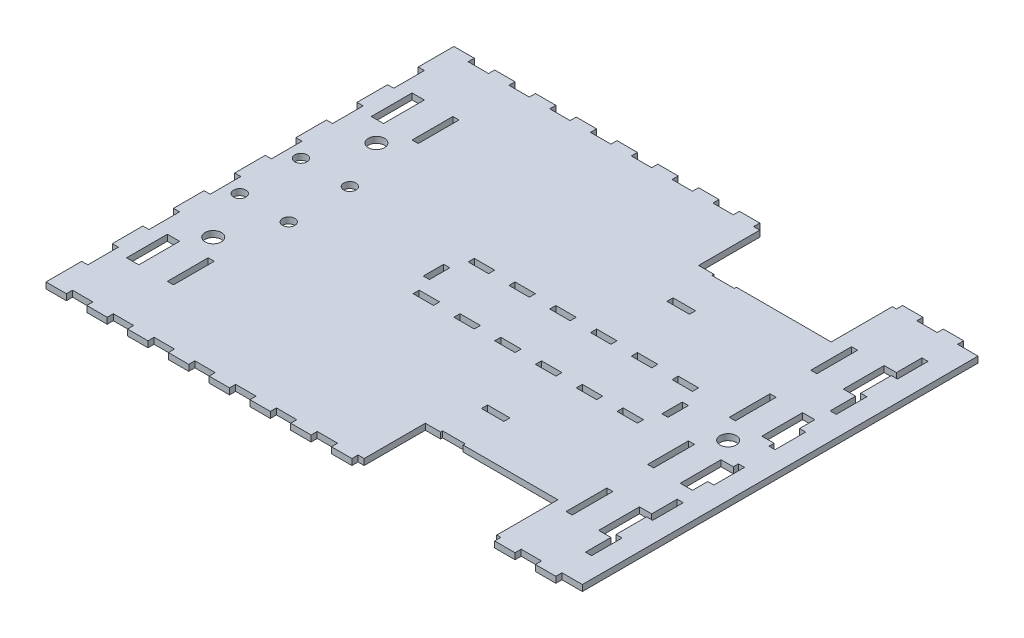
SolidWorks part; units mm, degrees
ref_plane "Front Plane" through (0, 0, 0) normal (0, 0, 1) x (1, 0, 0)
ref_plane "Top Plane" through (0, 0, 0) normal (0, 1, 0) x (1, 0, 0)
ref_plane "Right Plane" through (0, 0, 0) normal (1, 0, 0) x (0, 0, -1)
sketch "Sketch3" plane through (0, 0, 0) normal (0, 1, 0) x (1, 0, 0)
  line L0 (0, 0) -> (-300, 0) construction
  line L1 (-300, -97) -> (-300, 97)
  line L2 (-290, 100) -> (-300, 100)
  line L3 (-290, 97) -> (-290, 100)
  line L4 (-280, 97) -> (-290, 97)
  line L5 (-300, 100) -> (-300, 97)
  line L6 (-270, 100) -> (-280, 100)
  line L7 (-270, 97) -> (-270, 100)
  line L8 (-260, 97) -> (-270, 97)
  line L9 (-280, 100) -> (-280, 97)
  line L10 (-250, 100) -> (-260, 100)
  line L11 (-250, 97) -> (-250, 100)
  line L12 (-240, 97) -> (-250, 97)
  line L13 (-260, 100) -> (-260, 97)
  line L14 (-150, -100) -> (-150, 100) construction
  line L15 (-230, 100) -> (-240, 100)
  line L16 (-230, 97) -> (-230, 100)
  line L17 (-220, 97) -> (-230, 97)
  line L18 (-240, 100) -> (-240, 97)
  line L19 (-210, 100) -> (-220, 100)
  line L20 (-210, 97) -> (-210, 100)
  line L21 (-200, 97) -> (-210, 97)
  line L22 (-40, 97) -> (-40, -97)
  line L23 (-50, 37.5) -> (-53, 37.5)
  line L24 (-50, 7.5) -> (-53, 7.5)
  line L25 (-50, -45.947) -> (-50, 45.947) construction
  line L26 (-247, 37.5) -> (-250, 37.5) construction
  line L27 (-247, 7.5) -> (-250, 7.5) construction
  line L28 (-247, 48.5) -> (-247, -48.5) construction
  line L29 (-247, 48.5) -> (-223, 48.5) construction
  line L30 (-223, 48.5) -> (-223, -48.5) construction
  line L31 (-210, 15) -> (-90, 15) construction
  line L32 (-90, 15) -> (-90, 5) construction
  line L33 (-50, 7.5) -> (-50, 22.5)
  line L34 (-220, 100) -> (-220, 97)
  line L35 (-190, 100) -> (-200, 100)
  line L36 (-190, 97) -> (-190, 100)
  line L37 (-180, 97) -> (-190, 97)
  line L38 (-200, 100) -> (-200, 97)
  line L39 (-170, 100) -> (-180, 100)
  line L40 (-170, 97) -> (-170, 100)
  line L41 (-160, 97) -> (-170, 97)
  line L42 (-180, 100) -> (-180, 97)
  line L43 (-150, 100) -> (-160, 100)
  line L44 (-150, 97) -> (-150, 100)
  line L45 (-140, 97) -> (-150, 97)
  line L46 (-160, 100) -> (-160, 97)
  line L47 (-130, 100) -> (-140, 100)
  line L48 (-130, 97) -> (-130, 100)
  line L49 (-120, 97) -> (-130, 97)
  line L50 (-140, 100) -> (-140, 97)
  line L51 (-110, 100) -> (-120, 100)
  line L52 (-110, 97) -> (-110, 100)
  line L53 (-100, 97) -> (-110, 97)
  line L54 (-120, 100) -> (-120, 97)
  line L55 (-90, 100) -> (-100, 100)
  line L56 (-90, 97) -> (-90, 100)
  line L57 (-80, 97) -> (-90, 97)
  line L58 (-100, 100) -> (-100, 97)
  line L59 (-70, 100) -> (-80, 100)
  line L60 (-70, 97) -> (-70, 100)
  line L61 (-60, 97) -> (-70, 97)
  line L62 (-80, 100) -> (-80, 97)
  line L63 (-50, 100) -> (-60, 100)
  line L64 (-50, 97) -> (-50, 100)
  line L65 (-40, 97) -> (-50, 97)
  line L66 (-60, 100) -> (-60, 97)
  line L67 (-50, 22.5) -> (-53, 22.5)
  line L68 (-210, -15) -> (-90, -15) construction
  line L69 (-53, 7.5) -> (-53, 22.5)
  line L70 (-50, 37.5) -> (-50, 52.5)
  line L71 (-50, 52.5) -> (-53, 52.5)
  line L72 (-53, 37.5) -> (-53, 52.5)
  line L73 (-50, 67.5) -> (-53, 67.5)
  line L74 (-50, 67.5) -> (-50, 82.5)
  line L75 (-50, 82.5) -> (-53, 82.5)
  line L76 (-60, -100) -> (-60, -97)
  line L77 (-40, -97) -> (-50, -97)
  line L78 (-50, -97) -> (-50, -100)
  line L79 (-50, -100) -> (-60, -100)
  line L80 (-80, -100) -> (-80, -97)
  line L81 (-60, -97) -> (-70, -97)
  line L82 (-70, -97) -> (-70, -100)
  line L83 (-70, -100) -> (-80, -100)
  line L84 (-100, -100) -> (-100, -97)
  line L85 (-80, -97) -> (-90, -97)
  line L86 (-90, -97) -> (-90, -100)
  line L87 (-90, -100) -> (-100, -100)
  line L88 (-120, -100) -> (-120, -97)
  line L89 (-100, -97) -> (-110, -97)
  line L90 (-110, -97) -> (-110, -100)
  line L91 (-110, -100) -> (-120, -100)
  line L92 (-140, -100) -> (-140, -97)
  line L93 (-120, -97) -> (-130, -97)
  line L94 (-130, -97) -> (-130, -100)
  line L95 (-130, -100) -> (-140, -100)
  line L96 (-160, -100) -> (-160, -97)
  line L97 (-140, -97) -> (-150, -97)
  line L98 (-150, -97) -> (-150, -100)
  line L99 (-150, -100) -> (-160, -100)
  line L100 (-180, -100) -> (-180, -97)
  line L101 (-160, -97) -> (-170, -97)
  line L102 (-170, -97) -> (-170, -100)
  line L103 (-170, -100) -> (-180, -100)
  line L104 (-200, -100) -> (-200, -97)
  line L105 (-180, -97) -> (-190, -97)
  line L106 (-190, -97) -> (-190, -100)
  line L107 (-190, -100) -> (-200, -100)
  line L108 (-247, -48.5) -> (-223, -48.5) construction
  line L109 (-247, 7.5) -> (-247, 22.5) construction
  line L110 (-220, -100) -> (-220, -97)
  line L111 (-53, 67.5) -> (-53, 82.5)
  line L112 (-53, -67.5) -> (-53, -82.5)
  line L113 (-50, -82.5) -> (-53, -82.5)
  line L114 (-200, -97) -> (-210, -97)
  line L115 (-210, -97) -> (-210, -100)
  line L116 (-210, -100) -> (-220, -100)
  line L117 (-240, -100) -> (-240, -97)
  line L118 (-220, -97) -> (-230, -97)
  line L119 (-230, -97) -> (-230, -100)
  line L120 (-230, -100) -> (-240, -100)
  line L121 (-50, -67.5) -> (-50, -82.5)
  line L122 (-260, -100) -> (-260, -97)
  line L123 (-240, -97) -> (-250, -97)
  line L124 (-250, -97) -> (-250, -100)
  line L125 (-250, -100) -> (-260, -100)
  line L126 (-280, -100) -> (-280, -97)
  line L127 (-260, -97) -> (-270, -97)
  line L128 (-270, -97) -> (-270, -100)
  line L129 (-270, -100) -> (-280, -100)
  line L130 (-300, -100) -> (-300, -97)
  line L131 (-210, 15) -> (-210, -15) construction
  line L132 (-115, 15) -> (-125, 15)
  line L133 (-90, 5) -> (-93, 5)
  line L134 (-90, 5) -> (-90, -5)
  line L135 (-90, -5) -> (-93, -5)
  line L136 (-93, 5) -> (-93, -5)
  line L137 (-95, 15) -> (-105, 15)
  line L138 (-95, 15) -> (-95, 12)
  line L139 (-95, 12) -> (-105, 12)
  line L140 (-105, 15) -> (-105, 12)
  line L141 (-115, 12) -> (-125, 12)
  line L142 (-125, 15) -> (-125, 12)
  line L143 (-135, 15) -> (-145, 15)
  line L144 (-135, 12) -> (-145, 12)
  line L145 (-145, 15) -> (-145, 12)
  line L146 (-155, 15) -> (-165, 15)
  line L147 (-155, 12) -> (-165, 12)
  line L148 (-165, 15) -> (-165, 12)
  line L149 (-175, 15) -> (-185, 15)
  line L150 (-175, 12) -> (-185, 12)
  line L151 (-185, 15) -> (-185, 12)
  line L152 (-195, 15) -> (-205, 15)
  line L153 (-195, 12) -> (-205, 12)
  line L154 (-205, 15) -> (-205, 12)
  line L155 (-195, 12) -> (-195, 15)
  line L156 (-175, 12) -> (-175, 15)
  line L157 (-155, 12) -> (-155, 15)
  line L158 (-135, 12) -> (-135, 15)
  line L159 (-115, 12) -> (-115, 15)
  line L160 (-207, 5) -> (-207, -5)
  line L161 (-210, -5) -> (-207, -5)
  line L162 (-210, 5) -> (-210, -5)
  line L163 (-210, 5) -> (-207, 5)
  line L164 (-115, -12) -> (-115, -15)
  line L165 (-135, -12) -> (-135, -15)
  line L166 (-155, -12) -> (-155, -15)
  line L167 (-175, -12) -> (-175, -15)
  line L168 (-195, -12) -> (-195, -15)
  line L169 (-205, -15) -> (-205, -12)
  line L170 (-195, -12) -> (-205, -12)
  line L171 (-195, -15) -> (-205, -15)
  line L172 (-185, -15) -> (-185, -12)
  line L173 (-175, -12) -> (-185, -12)
  line L174 (-175, -15) -> (-185, -15)
  line L175 (-165, -15) -> (-165, -12)
  line L176 (-155, -12) -> (-165, -12)
  line L177 (-155, -15) -> (-165, -15)
  line L178 (-145, -15) -> (-145, -12)
  line L179 (-135, -12) -> (-145, -12)
  line L180 (-135, -15) -> (-145, -15)
  line L181 (-125, -15) -> (-125, -12)
  line L182 (-115, -12) -> (-125, -12)
  line L183 (-105, -15) -> (-105, -12)
  line L184 (-95, -12) -> (-105, -12)
  line L185 (-95, -15) -> (-95, -12)
  line L186 (-95, -15) -> (-105, -15)
  line L187 (-115, -15) -> (-125, -15)
  line L188 (-247, 22.5) -> (-250, 22.5) construction
  line L189 (-250, 7.5) -> (-250, 22.5) construction
  line L190 (-247, 37.5) -> (-247, 52.5) construction
  line L191 (-247, 52.5) -> (-250, 52.5) construction
  line L192 (-250, 37.5) -> (-250, 52.5) construction
  line L193 (-247, 67.5) -> (-250, 67.5) construction
  line L194 (-247, 67.5) -> (-247, 82.5) construction
  line L195 (-247, 82.5) -> (-250, 82.5) construction
  line L196 (-250, 67.5) -> (-250, 82.5) construction
  line L197 (-250, -67.5) -> (-250, -82.5) construction
  line L198 (-247, -82.5) -> (-250, -82.5) construction
  line L199 (-247, -67.5) -> (-247, -82.5) construction
  line L200 (-247, -67.5) -> (-250, -67.5) construction
  line L201 (-250, -37.5) -> (-250, -52.5) construction
  line L202 (-247, -52.5) -> (-250, -52.5) construction
  line L203 (-247, -37.5) -> (-247, -52.5) construction
  line L204 (-250, -7.5) -> (-250, -22.5) construction
  line L205 (-247, -22.5) -> (-250, -22.5) construction
  line L206 (-247, -7.5) -> (-247, -22.5) construction
  line L207 (-247, -7.5) -> (-250, -7.5) construction
  line L208 (-247, -37.5) -> (-250, -37.5) construction
  line L209 (-50, -67.5) -> (-53, -67.5)
  line L210 (-53, -37.5) -> (-53, -52.5)
  line L211 (-50, -52.5) -> (-53, -52.5)
  line L212 (-50, -37.5) -> (-50, -52.5)
  line L213 (-53, -7.5) -> (-53, -22.5)
  line L214 (-50, -22.5) -> (-53, -22.5)
  line L215 (-50, -7.5) -> (-50, -22.5)
  line L216 (-50, -7.5) -> (-53, -7.5)
  line L217 (-50, -37.5) -> (-53, -37.5)
  line L231 (-280, -97) -> (-290, -97)
  line L232 (-290, -97) -> (-290, -100)
  line L233 (-290, -100) -> (-300, -100)
  circle A0 centre (-290, 15) radius 3
  circle A1 centre (-266, 15) radius 3
  circle A2 centre (-266, -15) radius 3
  circle A3 centre (-290, -15) radius 3
  point P31 (-250, 36)
  point P80 (-91.5, 0)
  point P82 (-150, 0)
  point P126 (-223, 0)
  point P128 (-250, 18)
  point P129 (-50, 0)
  point P150 (-150, -15)
  point P151 (-150, 15)
  point P183 (-208.5, 0)
  point P212 (-223, 18)
  point P218 (-223, 36)
  dimension "D17" = 6
  dimension "D18" = 6
  dimension "D1" = 300
  dimension "D4" = 7.5
  dimension "D5" = 100
  dimension "D6" = 97
  dimension "D7" = 15
  dimension "D8" = 97
  dimension "D9" = 3
  dimension "D10" = 3
  dimension "D11" = 48.5
  dimension "D12" = 24
  dimension "D13" = 60
  dimension "D14" = 15
  dimension "D15" = 24
  dimension "D16" = 15
  dimension "D19" = 194
  dimension "D20" = 10
  dimension "D21" = 3
  dimension "D22" = 7.5
  dimension "D23" = 15
  dimension "D24" = 3
  dimension "D25" = 3
  dimension "D29" = 10
  dimension "D30" = 3
  dimension "D31" = 10
  dimension "D32" = 3
  dimension "D33" = 10
  dimension "D34" = 5
  dimension "D35" = 6
  dimension "D36" = 3
extrude "Boss-Extrude1" add sketch "Sketch3" along normal blind 3 contours L1 L116 L115 L107 L106 L83 L82 L79 L95 L98 L99 L91 L90 L86 region at (-170.6363, 0, 0)
sketch "Sketch5" plane through (0, 3, 0) normal (0, 1, 0) x (1, 0, 0)
  line L0 (-82, 0) -> (-82, 67) construction
  line L2 (-82, 67) -> (-128.5, 67)
  line L3 (-82, 67) -> (-82, 97)
  line L4 (-82, 97) -> (-147, 97)
  line L5 (-147, 67) -> (-147, 97)
  line L7 (-110, 100) -> (-120, 100) construction
  line L8 (-82, 0) -> (-300, 0) construction
  line L9 (-300, 100) -> (-300, -100) construction
  line L10 (-147, -67) -> (-147, -97)
  line L11 (-82, -97) -> (-147, -97)
  line L12 (-82, -67) -> (-82, -97)
  line L13 (-82, -67) -> (-128.5, -67)
  line L14 (-114.5, -67) -> (-114.5, -47) construction
  line L15 (-114.5, -47) -> (-128.5, -47) construction
  line L16 (-128.5, -47) -> (-128.5, -44)
  line L17 (-128.5, -44) -> (-139.5, -44)
  line L18 (-139.5, -44) -> (-139.5, -47)
  line L19 (-139.5, -47) -> (-128.5, -47)
  line L20 (-128.5, -67) -> (-128.5, -66)
  line L21 (-128.5, -66) -> (-139.5, -66)
  line L22 (-139.5, -66) -> (-139.5, -67)
  line L23 (-139.5, -67) -> (-147, -67)
  line L24 (-114.5, 47) -> (-128.5, 47) construction
  line L25 (-114.5, 67) -> (-114.5, 47) construction
  line L26 (-139.5, 66) -> (-139.5, 67)
  line L27 (-128.5, 66) -> (-139.5, 66)
  line L28 (-128.5, 67) -> (-128.5, 66)
  line L29 (-139.5, 47) -> (-128.5, 47)
  line L30 (-139.5, 44) -> (-139.5, 47)
  line L31 (-128.5, 44) -> (-139.5, 44)
  line L32 (-128.5, 47) -> (-128.5, 44)
  line L33 (-139.5, 67) -> (-147, 67)
  dimension "D2" = 30
  dimension "D3" = 3
  dimension "D5" = 14
  dimension "D6" = 3
  dimension "D7" = 11
  dimension "D8" = 20
  dimension "D9" = 1
extrude "Cut-Extrude2" cut sketch "Sketch5" against normal blind 10 contours L5 L2 L3 L4 | L12 L13 L10 L11 | L31 L30 L29 L32 | L17 L18 L19 L16 region at (-114.6094, 3, -81.9131) region at (-114.6094, 3, 81.9131) body kept at (-300, 0, -100)
sketch "Croquis1" plane through (0, 3, 0) normal (0, 1, 0) x (1, 0, 0)
  line L0 (-300, -67.5) -> (-300, -82.5)
  line L25 (-300, 100) -> (-300, -100) construction
  line L26 (-300, 37.5) -> (-300, 52.5)
  line L27 (-297, 37.5) -> (-300, 37.5)
  line L28 (-297, 7.5) -> (-300, 7.5)
  line L29 (-300, -7.5) -> (-297, -7.5)
  line L30 (-297, -22.5) -> (-300, -22.5)
  line L31 (-297, -7.5) -> (-297, -22.5)
  line L32 (-297, 82.5) -> (-297, 67.5)
  line L33 (-300, -22.5) -> (-300, -7.5)
  line L34 (-297, -37.5) -> (-297, -52.5)
  line L35 (-297, 67.5) -> (-300, 67.5)
  line L36 (-300, 67.5) -> (-300, 82.5)
  line L37 (-297, 52.5) -> (-297, 37.5)
  line L38 (-300, 22.5) -> (-297, 22.5)
  line L39 (-300, -37.5) -> (-297, -37.5)
  line L40 (-297, -52.5) -> (-300, -52.5)
  line L41 (-300, 52.5) -> (-297, 52.5)
  line L42 (-300, -52.5) -> (-300, -37.5)
  line L43 (-300, 82.5) -> (-297, 82.5)
  line L44 (-297, 22.5) -> (-297, 7.5)
  line L45 (-300, 7.5) -> (-300, 22.5)
  line L46 (-300, -67.5) -> (-297, -67.5)
  line L47 (-297, -67.5) -> (-297, -82.5)
  line L48 (-297, -82.5) -> (-300, -82.5)
extrude "Cortar-Extruir1" cut sketch "Croquis1" against normal blind 10
sketch "Croquis2" plane through (0, 3, 0) normal (0, 1, 0) x (1, 0, 0)
  line L0 (-40, 0) -> (-53, 0) construction
  line L1 (-40, 97) -> (-40, -97) construction
  line L2 (-53, 10) -> (-53, -10) construction
  line L3 (-53, -7.5) -> (-53, -22.5) construction
  line L4 (-53, -10) -> (-59, -10)
  line L5 (-59, -10) -> (-59, -30)
  line L6 (-59, -30) -> (-53, -30)
  line L7 (-53, -30) -> (-53, -10)
  line L8 (-53, -30) -> (-53, -50) construction
  line L9 (-53, -37.5) -> (-53, -52.5) construction
  line L10 (-53, -50) -> (-59, -50)
  line L11 (-59, -50) -> (-59, -70)
  line L12 (-59, -70) -> (-53, -70)
  line L13 (-53, -67.5) -> (-53, -82.5) construction
  line L14 (-53, -70) -> (-53, -50)
  line L15 (-53, 30) -> (-53, 50) construction
  line L16 (-53, 70) -> (-53, 50)
  line L17 (-59, 70) -> (-53, 70)
  line L18 (-59, 50) -> (-59, 70)
  line L19 (-53, 50) -> (-59, 50)
  line L20 (-53, 30) -> (-53, 10)
  line L21 (-59, 30) -> (-53, 30)
  line L22 (-59, 10) -> (-59, 30)
  line L23 (-53, 10) -> (-59, 10)
  line L24 (-59, 70) -> (-72, 70) construction
  line L25 (-72, 70) -> (-75, 70)
  line L26 (-72, 70) -> (-72, 50)
  line L27 (-72, 50) -> (-75, 50)
  line L28 (-75, 50) -> (-75, 70)
  line L29 (-72, 30) -> (-75, 30)
  line L30 (-75, 30) -> (-75, 10)
  line L31 (-75, 10) -> (-72, 10)
  line L32 (-72, 10) -> (-72, 30)
  line L33 (-72, -10) -> (-75, -10)
  line L34 (-75, -10) -> (-75, -30)
  line L35 (-75, -30) -> (-72, -30)
  line L36 (-72, -30) -> (-72, -10)
  line L37 (-72, -50) -> (-75, -50)
  line L38 (-75, -50) -> (-75, -70)
  line L39 (-75, -70) -> (-72, -70)
  line L40 (-72, -70) -> (-72, -50)
  line L45 (-290.5, 30) -> (-290.5, 50) construction
  line L46 (-290.5, -30) -> (-290.5, -50) construction
  line L49 (-270.5, -70) -> (-270.5, -50)
  line L50 (-267.5, -70) -> (-270.5, -70)
  line L51 (-267.5, -50) -> (-267.5, -70)
  line L52 (-270.5, -50) -> (-267.5, -50)
  line L61 (-267.5, 50) -> (-267.5, 70)
  line L62 (-270.5, 50) -> (-267.5, 50)
  line L63 (-270.5, 70) -> (-270.5, 50)
  line L64 (-270.5, 70) -> (-267.5, 70)
  line L69 (-290.5, 50) -> (-284.5, 50)
  line L70 (-284.5, 50) -> (-284.5, 70)
  line L71 (-284.5, 70) -> (-290.5, 70)
  line L72 (-290.5, 70) -> (-290.5, 50)
  line L73 (-290.5, -70) -> (-290.5, -50)
  line L74 (-284.5, -70) -> (-290.5, -70)
  line L75 (-284.5, -50) -> (-284.5, -70)
  line L76 (-290.5, -50) -> (-284.5, -50)
  circle A0 centre (-65.5, 0) radius 4
  circle A3 centre (-278, -40) radius 4
  circle A4 centre (-278, 40) radius 4
  dimension "D8" = 8
  dimension "D11" = 8
  dimension "D12" = 8
  dimension "D1" = 10
  dimension "D2" = 6
  dimension "D3" = 20
  dimension "D4" = 20
  dimension "D5" = 13
  dimension "D6" = 3
  dimension "D7" = 20
  dimension "D9" = 14
extrude "Cortar-Extruir2" cut sketch "Croquis2" against normal blind 10
